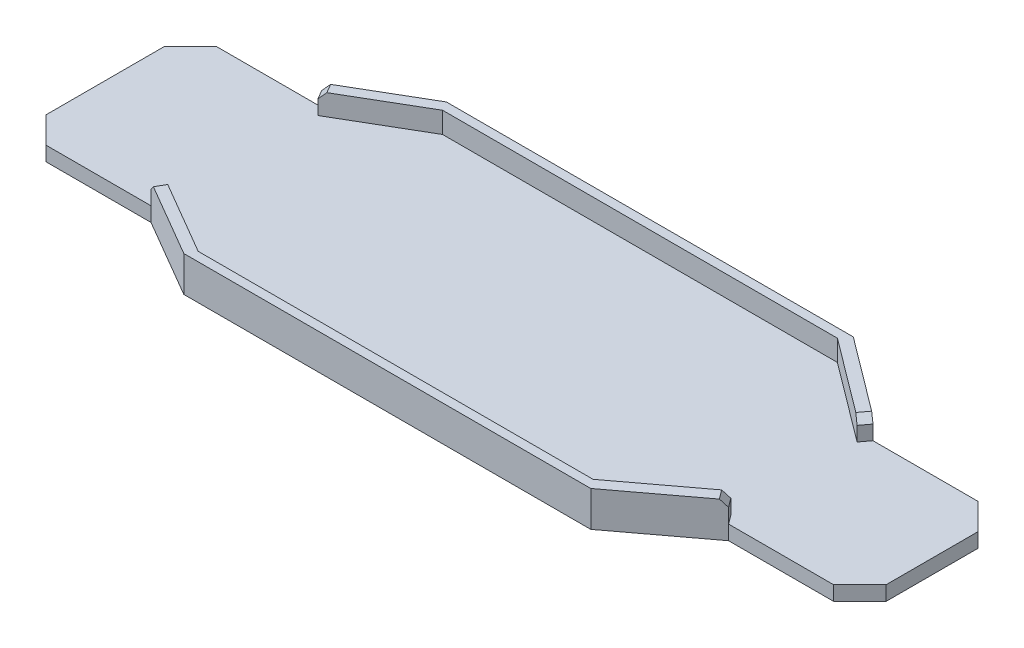
SolidWorks part; units mm, degrees
ref_plane "Front Plane" through (0, 0, 0) normal (0, 0, 1) x (1, 0, 0)
ref_plane "Top Plane" through (0, 0, 0) normal (0, 1, 0) x (1, 0, 0)
ref_plane "Right Plane" through (0, 0, 0) normal (1, 0, 0) x (0, 0, -1)
sketch "Sketch1" plane through (0, 0, 0) normal (0, 1, 0) x (1, 0, 0)
  line L0 (-235.1499, 0) -> (235.1499, 0) construction
  line L1 (0, 0) -> (0, 52596.8311) construction
  line L2 (-107.5, 32.5) -> (-77.5, 50)
  line L3 (-77.5, 50) -> (77.5, 50)
  line L4 (-107.5, 32.5) -> (-157.5, 32.5)
  line L5 (-157.5, 32.5) -> (-157.5, -32.5)
  line L6 (-77.5, -50) -> (77.5, -50)
  line L7 (-107.5, -32.5) -> (-77.5, -50)
  line L8 (-107.5, -32.5) -> (-157.5, -32.5)
  line L9 (77.5, 50) -> (107.5, 27.5)
  line L10 (107.5, 27.5) -> (157.5, 27.5)
  line L11 (157.5, 27.5) -> (157.5, -27.5)
  line L12 (107.5, -27.5) -> (157.5, -27.5)
  line L13 (77.5, -50) -> (107.5, -27.5)
  point P3 (0, 0)
  point P10 (-92.5, 41.25)
  point P15 (-92.5, -41.25)
  point P18 (-157.5, 0)
  point P19 (0, -50)
  point P20 (0, 50)
  point P23 (157.5, 0)
  dimension "D1" = 50
  dimension "D2" = 65
  dimension "D3" = 30
  dimension "D4" = 50
  dimension "D5" = 155
  dimension "D6" = 50
  dimension "D7" = 55
  dimension "D8" = 30
extrude "Boss-Extrude1" add sketch "Sketch1" along normal blind 5.5
sketch "Sketch3" plane through (0, 5.5, 0) normal (0, 1, 0) x (1, 0, 0)
  line L0 (0, 0) -> (50000, 0) construction
  line L1 (0, 0) -> (0, 50000) construction
  line L2 (0, 50) -> (-77.5, 50)
  line L3 (77.5, 50) -> (-77.5, 50) construction
  line L4 (-77.5, 50) -> (-107.5, 32.5)
  line L5 (-107.5, 32.5) -> (-105.4845, 29.0449)
  line L6 (-105.4845, 29.0449) -> (-75.4845, 46.5449)
  line L7 (-75.4845, 46.5449) -> (0, 46.5449)
  line L8 (-77.5, 50) -> (-75.4845, 46.5449) construction
  line L9 (0, 50) -> (77.5, 50)
  line L10 (77.5, 50) -> (107.5, 27.5)
  line L11 (107.5, 27.5) -> (104.9087, 24.0449)
  line L12 (104.9087, 24.0449) -> (74.9087, 46.5449)
  line L13 (74.9087, 46.5449) -> (0, 46.5449)
  line L14 (74.9087, 46.5449) -> (77.5, 50) construction
  line L15 (74.9087, -46.5449) -> (77.5, -50) construction
  line L16 (-77.5, -50) -> (-75.4845, -46.5449) construction
  line L17 (74.9087, -46.5449) -> (0, -46.5449)
  line L18 (104.9087, -24.0449) -> (74.9087, -46.5449)
  line L19 (107.5, -27.5) -> (104.9087, -24.0449)
  line L20 (77.5, -50) -> (107.5, -27.5)
  line L21 (0, -50) -> (77.5, -50)
  line L22 (-75.4845, -46.5449) -> (0, -46.5449)
  line L23 (-105.4845, -29.0449) -> (-75.4845, -46.5449)
  line L24 (-107.5, -32.5) -> (-105.4845, -29.0449)
  line L25 (-77.5, -50) -> (-107.5, -32.5)
  line L26 (0, -50) -> (-77.5, -50)
  dimension "D1" = 4
extrude "Chassis-Walls1" add sketch "Sketch3" along normal blind 8
chamfer "Chamfer1" distance 10 angle 45 2 edges at (-157.5, 2.75, -32.5) (-157.5, 2.75, 32.5)
chamfer "Chamfer2" distance 10 angle 45 2 edges at (157.5, 2.75, -27.5) (157.5, 2.75, 27.5)
chamfer "Chamfer3" distance 2.5 angle 45 4 edges at (-106.4923, 13.5, -30.7724) (-106.4923, 13.5, 30.7724) (106.2043, 13.5, 25.7724) (106.2043, 13.5, -25.7724)
sketch "Sketch4" plane through (0, 5.5, 0) normal (0, 1, 0) x (1, 0, 0)
  line L0 (147.5, 27.5) -> (107.5, 27.5) construction
  line L1 (127.5, 27.5) -> (127.5, -27.5) construction
  line L2 (107.5, -27.5) -> (147.5, -27.5) construction
  line L3 (126, 27.5) -> (126, -27.5) construction
  line L4 (126, -27.5) -> (129, -27.5) construction
  line L5 (126, 27.5) -> (129, 27.5) construction
  line L6 (129, 27.5) -> (129, -27.5) construction
  line L7 (-127.5, 32.5) -> (-127.5, -32.5) construction
  line L8 (-107.5, 32.5) -> (-147.5, 32.5) construction
  line L9 (-147.5, -32.5) -> (-107.5, -32.5) construction
  line L10 (-126, 32.5) -> (-129, 32.5) construction
  line L11 (-129, 32.5) -> (-129, -32.5) construction
  line L12 (-129, -32.5) -> (-126, -32.5) construction
  line L13 (-126, 32.5) -> (-126, -32.5) construction
  line L14 (0, 0) -> (50000, 0) construction
  line L15 (0, 0) -> (0, 50000) construction
  line L16 (67.5, 20) -> (-67.5, 20)
  line L17 (-67.5, 20) -> (-67.5, -20)
  line L18 (67.5, 20) -> (67.5, -20)
  line L19 (67.5, -20) -> (-67.5, -20)
  line L21 (-136.5, 22.5) -> (-111.5, 22.5)
  line L22 (-136.5, 22.5) -> (-136.5, -22.5)
  line L23 (-136.5, -22.5) -> (-111.5, -22.5)
  line L24 (-111.5, 22.5) -> (-111.5, -22.5)
  line L25 (-136.5, 22.5) -> (-111.5, -22.5) construction
  line L26 (-136.5, -22.5) -> (-111.5, 22.5) construction
  line L27 (110, 7) -> (145, 7)
  line L28 (110, 7) -> (110, -7)
  line L29 (110, -7) -> (145, -7)
  line L30 (145, 7) -> (145, -7)
  line L31 (110, 7) -> (145, -7) construction
  line L32 (110, -7) -> (145, 7) construction
  circle A0 centre (-147.5, 15) radius 2
  circle A1 centre (-102.5, 15) radius 2
  circle A2 centre (-102.5, -15) radius 2
  circle A3 centre (-147.5, -15) radius 2
  circle A4 centre (140.5, 15) radius 2
  circle A5 centre (115.5, 15) radius 2
  circle A6 centre (115.5, -15) radius 2
  circle A7 centre (140.5, -15) radius 2
  point P28 (0, -20)
  point P30 (0, 20)
  point P31 (67.5, 0)
  point P32 (-67.5, 0)
  point P49 (-124, 0)
  point P54 (127.5, 0)
  dimension "D7" = 4
  dimension "D8" = 4
  dimension "D11" = 4
  dimension "D16" = 4
  dimension "D1" = 3
  dimension "D2" = 3
  dimension "D3" = 40
  dimension "D4" = 135
  dimension "D5" = 20
  dimension "D6" = 15
  dimension "D9" = 15
  dimension "D10" = 25
  dimension "D12" = 15
  dimension "D13" = 15
  dimension "D14" = 12
  dimension "D15" = 13
  dimension "D17" = 25
  dimension "D18" = 45
  dimension "D19" = 16
  dimension "D20" = 14
  dimension "D21" = 35
split line "Split Line1" [suppressed]
